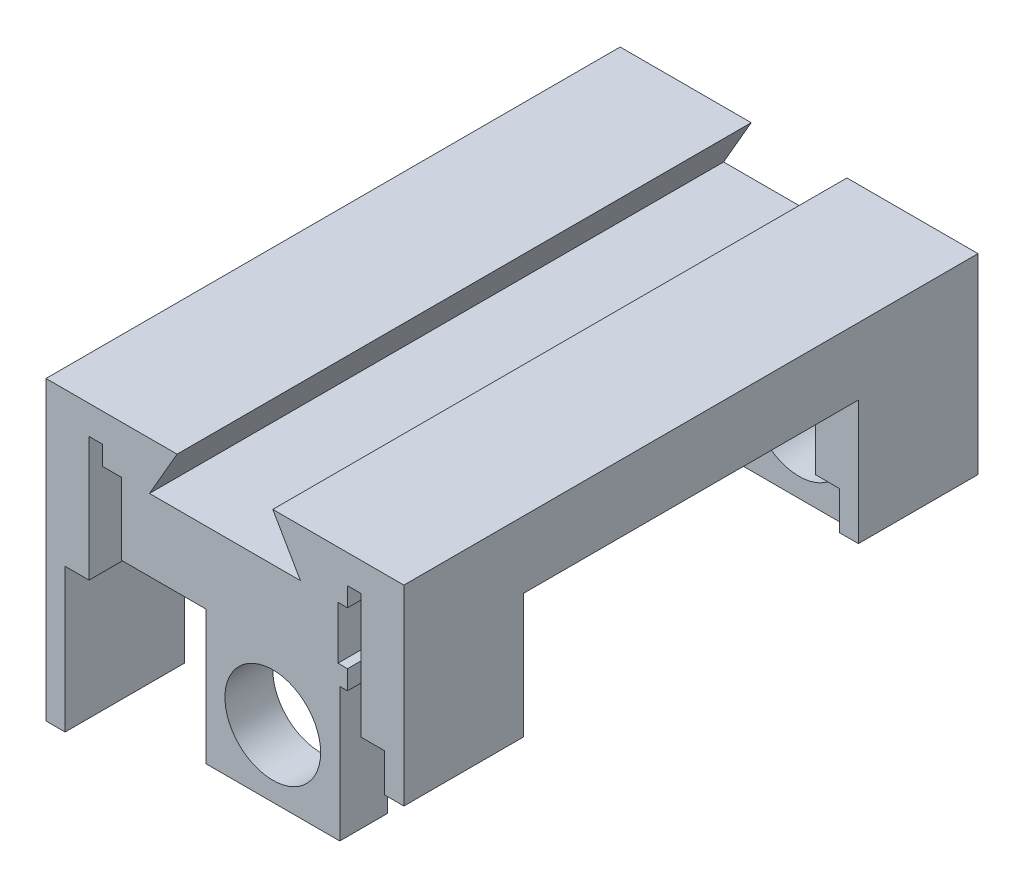
SolidWorks part; units mm, degrees
ref_plane "Front Plane" through (0, 0, 0) normal (0, 0, 1) x (1, 0, 0)
ref_plane "Top Plane" through (0, 0, 0) normal (0, 1, 0) x (1, 0, 0)
ref_plane "Right Plane" through (0, 0, 0) normal (1, 0, 0) x (0, 0, -1)
sketch "Sketch1" plane through (0, 0, 0) normal (0, 0, 1) x (1, 0, 0)
  line L0 (-16.27, 9.51) -> (16.27, 9.51)
  line L3 (21.209, 5.08) -> (21.209, 0)
  line L4 (21.209, 0) -> (23.749, 0)
  line L5 (23.749, 0) -> (23.749, 25.4)
  line L10 (23.749, 25.4) -> (-23.749, 25.4)
  line L11 (-23.749, 25.4) -> (-23.749, 0)
  line L12 (-23.749, 0) -> (-21.209, 0)
  line L13 (-21.209, 0) -> (-21.209, 5.08)
  line L16 (-16.27, 9.51) -> (-16.27, 12.05)
  line L17 (-16.27, 12.05) -> (-15, 12.05)
  line L18 (-15, 12.05) -> (-15, 19.05)
  line L19 (-15, 19.05) -> (-16.27, 19.05)
  line L20 (-16.27, 19.05) -> (-16.27, 21.59)
  line L21 (16.27, 21.59) -> (16.27, 19.05)
  line L22 (16.27, 19.05) -> (15, 19.05)
  line L23 (15, 19.05) -> (15, 12.05)
  line L24 (15, 12.05) -> (16.27, 12.05)
  line L25 (16.27, 12.05) -> (16.27, 9.51)
  line L26 (-16.27, 21.59) -> (-18.034, 21.59)
  line L27 (-18.034, 21.59) -> (-18.034, 5.08)
  line L28 (-18.034, 5.08) -> (-21.209, 5.08)
  line L29 (16.27, 21.59) -> (18.034, 21.59)
  line L30 (18.034, 21.59) -> (18.034, 5.08)
  line L31 (18.034, 5.08) -> (21.209, 5.08)
  line L32 (0, 0) -> (0, 9.51) construction
  point P5 (23.749, 31.75)
  point P8 (23.0292, 31.75)
  dimension "D1" = 30
  dimension "D2" = 7
  dimension "D3" = 1.27
  dimension "D4" = 42.418
  dimension "D5" = 2.54
  dimension "D9" = 25.4
  dimension "D10" = 2.54
  dimension "D11" = 5.08
  dimension "D12" = 3.175
  dimension "D13" = 3.81
  dimension "D14" = 2.54
extrude "Boss-Extrude1" add sketch "Sketch1" along normal blind 76.2
sketch "Sketch2" plane through (0, 0, 76.2) normal (0, 0, 1) x (1, 0, 0)
  line L0 (-21.209, 5.08) -> (-23.749, 5.08)
  line L1 (-23.749, 25.4) -> (-23.749, 0) construction
  line L2 (-23.749, 5.08) -> (-23.749, -13.97)
  line L3 (-23.749, -13.97) -> (-21.209, -13.97)
  line L4 (-21.209, -13.97) -> (-21.209, 5.08)
  line L5 (-21.209, 5.08) -> (-18.034, 5.08) construction
  dimension "D1" = 19.05
extrude "Boss-Extrude2" add sketch "Sketch2" against normal up to surface (76.2 mm away) up to face at (0, 12.5375, 0)
sketch "Sketch3" plane through (0, 0, 76.2) normal (0, 0, 1) x (1, 0, 0)
  line L0 (-2.54, 9.51) -> (15.24, 9.51)
  line L2 (15.24, 9.51) -> (15.24, -8.27)
  line L3 (15.24, -8.27) -> (-2.54, -8.27)
  line L4 (-2.54, -8.27) -> (-2.54, 9.51)
  line L6 (-2.54, 9.51) -> (15.24, -8.27) construction
  line L7 (-16.27, 9.51) -> (16.27, 9.51) construction
  circle A0 centre (6.35, 0.62) radius 6.35
  point P2 (0, -1.2263)
  point P3 (6.0712, -1.2968)
  point P8 (28.829, 0)
  point P11 (39.4153, -10.5863)
  point P12 (5.6303, 0.62)
  dimension "D2" = 12.7
  dimension "D1" = 2.54
  dimension "D3" = 6.35
extrude "Boss-Extrude3" add sketch "Sketch3" against normal blind 6.35
ref_plane "Plane1" through (0, 0, 38.1) normal (0, 0, 1) x (1, 0, 0)
mirror "Mirror1" about plane through (0, 0, 38.1) normal (0, 0, 1) of "Boss-Extrude3"
sketch "Sketch4" plane through (0, 0, 76.2) normal (0, 0, 1) x (1, 0, 0)
  line L0 (-6.35, 25.4) -> (-10.0162, 19.05)
  line L1 (23.749, 25.4) -> (-23.749, 25.4) construction
  line L2 (-10.0162, 19.05) -> (10.0162, 19.05)
  line L3 (10.0162, 19.05) -> (6.35, 25.4)
  line L4 (6.35, 25.4) -> (-6.35, 25.4)
  point P5 (0, 25.4)
  point P7 (0, 25.4)
  dimension "D1" = 60
  dimension "D2" = 12.7
  dimension "D3" = 6.35
extrude "Cut-Extrude1" cut sketch "Sketch4" against normal through all
sketch "Sketch5" plane through (23.749, 0, 0) normal (1, 0, 0) x (0, 0, -1)
  line L0 (0, -13.97) -> (-76.2, -13.97) construction
  line L1 (-60.325, -13.97) -> (-15.875, -13.97)
  line L2 (-60.325, -13.97) -> (-60.325, 16.51)
  line L3 (-60.325, 16.51) -> (-15.875, 16.51)
  line L4 (-15.875, -13.97) -> (-15.875, 16.51)
  point P6 (-38.1, -13.97)
  point P7 (-38.1, -13.97)
  dimension "D1" = 44.45
  dimension "D2" = 30.48
extrude "Cut-Extrude2" cut sketch "Sketch5" against normal through all
sketch "Sketch6" plane through (0, 0, 76.2) normal (0, 0, 1) x (1, 0, 0)
  line L0 (-16.27, 9.51) -> (-2.54, 9.51) construction
  line L1 (-16.27, 19.05) -> (-13.73, 19.05)
  line L2 (-16.27, 19.05) -> (-16.27, 9.51)
  line L3 (-16.27, 9.51) -> (-13.73, 9.51)
  line L4 (-13.73, 19.05) -> (-13.73, 9.51)
  point P7 (0, 0)
  point P8 (-16.27, 19.05)
  dimension "D1" = 2.54
extrude "Cut-Extrude3" cut sketch "Sketch6" against normal up to surface (76.2 mm away) up to face at (0.7938, 11.3856, 0)
